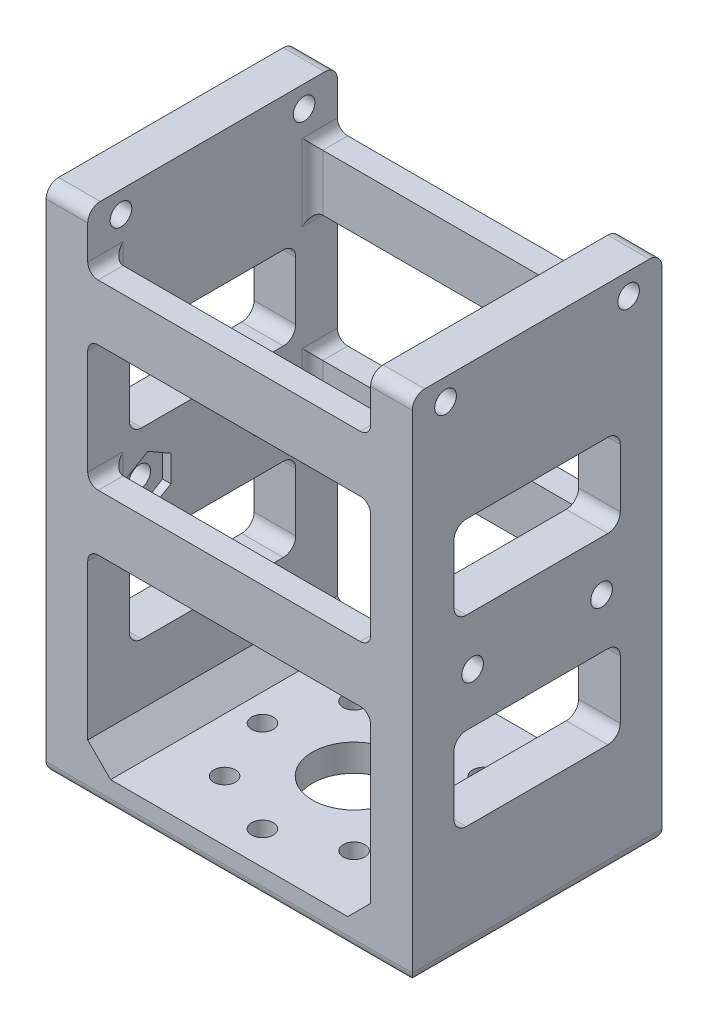
SolidWorks part; units mm, degrees
ref_plane "Front Plane" through (0, 0, 0) normal (0, 0, 1) x (1, 0, 0)
ref_plane "Top Plane" through (0, 0, 0) normal (0, 1, 0) x (1, 0, 0)
ref_plane "Right Plane" through (0, 0, 0) normal (1, 0, 0) x (0, 0, -1)
sketch "Sketch1" plane through (0, 0, 0) normal (0, 1, 0) x (1, 0, 0)
  line L1 (0, 0) -> (44, 0)
  line L2 (0, 0) -> (0, 30)
  line L3 (0, 30) -> (44, 30)
  line L4 (44, 0) -> (44, 30)
  dimension "D1" = 30
  dimension "D2" = 44
extrude "Boss-Extrude1" add sketch "Sketch1" along normal blind 54.5
sketch "Sketch5" plane through (0, 54.5, 0) normal (0, 1, 0) x (1, 0, 0)
  line L0 (0, 0) -> (44, 0) construction
  line L1 (0, 30) -> (5, 30)
  line L2 (0, 30) -> (0, 0)
  line L3 (0, 0) -> (5, 0)
  line L4 (5, 30) -> (5, 0)
  dimension "D1" = 5
ref_plane "Plane1" through (22, 0, 0) normal (-1, 0, 0) x (0, 0, 1)
extrude "Boss-Extrude3" add sketch "Sketch5" along normal blind 6.8
sketch "Sketch9" plane through (5, 0, 0) normal (1, 0, 0) x (0, 0, -1)
  line L0 (30, 61.3) -> (30, 54.5) construction
  line L2 (0, 61.3) -> (0, 54.5) construction
  line L4 (0, 61.3) -> (30, 61.3) construction
  circle A0 centre (26, 58.7) radius 1.3
  circle A1 centre (4, 58.7) radius 1.3
  dimension "D1" = 2.6
  dimension "D2" = 4
  dimension "D3" = 2.6
  dimension "D4" = 2.6
  dimension "D5" = 4
  dimension "D6" = 2.6
extrude "Cut-Extrude6" cut sketch "Sketch9" against normal through all
mirror "Mirror2" about plane through (22, 0, 0) normal (-1, 0, 0) of "Boss-Extrude3", "Cut-Extrude6"
fillet "Fillet1" radius 1.5 4 edges at (41.5, 61.3, -30) (2.5, 61.3, -30) (2.5, 61.3, 0) (41.5, 61.3, 0)
fillet "Fillet2" radius 1.25 4 edges at (0, 0, -15) (22, 0, -30) (22, 0, 0) (44, 0, -15)
sketch "Sketch11" plane through (0, 54.5, 0) normal (0, 1, 0) x (1, 0, 0)
  line L0 (39, 0) -> (39, 30) construction
  line L1 (39, 27) -> (5, 27)
  line L2 (39, 27) -> (39, 3)
  line L3 (39, 3) -> (5, 3)
  line L4 (5, 27) -> (5, 3)
  line L5 (5, 0) -> (5, 30) construction
  line L6 (39, 30) -> (5, 30) construction
  line L7 (5, 0) -> (39, 0) construction
  dimension "D1" = 3
  dimension "D2" = 3
extrude "Cut-Extrude7" cut sketch "Sketch11" against normal blind 51.25
ref_point "Point1"
sketch "Sketch13" plane through (0, 0, 0) normal (0, -1, 0) x (1, 0, 0)
  circle A0 centre (22, -15) radius 5
  circle A1 centre (33, -15) radius 1.3
  dimension "D1" = 10
  dimension "D2" = 2.6
  dimension "D3" = 11
extrude "Cut-Extrude8" cut sketch "Sketch13" against normal blind 3.5
ref_axis "Axis1" through (22, 0, -15) along (0, -1, 0)
pattern_circular "CirPattern1" count 8 over 360 about axis through (22, 0, -15) along (0, -1, 0) of "Cut-Extrude8"
ref_plane "Plane2" through (0, 0, -15) normal (0, 0, -1) x (-1, 0, 0)
sketch "Sketch15" plane through (44, 0, 0) normal (1, 0, 0) x (0, 0, -1)
  line L0 (0, 1.25) -> (30, 1.25) construction
  line L1 (25, 13.25) -> (5, 13.25)
  line L2 (25, 13.25) -> (25, 23.25)
  line L3 (25, 23.25) -> (5, 23.25)
  line L4 (5, 13.25) -> (5, 23.25)
  line L5 (30, 59.8) -> (30, 1.25) construction
  line L6 (0, 59.8) -> (0, 1.25) construction
  line L8 (25, 35.25) -> (5, 35.25)
  line L9 (25, 35.25) -> (25, 45.25)
  line L10 (25, 45.25) -> (5, 45.25)
  line L11 (5, 35.25) -> (5, 45.25)
  dimension "D1" = 12
  dimension "D2" = 10
  dimension "D3" = 5
  dimension "D4" = 5
  dimension "D5" = 12
  dimension "D6" = 10
extrude "Cut-Extrude10" cut sketch "Sketch15" against normal up to next
fillet "Fillet6" radius 1.5 8 edges at (41.5, 13.25, -5) (41.5, 35.25, -5) (41.5, 23.25, -5) (41.5, 45.25, -5) (41.5, 23.25, -25) (41.5, 45.25, -25) (41.5, 35.25, -25) (41.5, 13.25, -25)
mirror "Mirror4" about plane through (22, 0, 0) normal (-1, 0, 0) of "Cut-Extrude10", "Fillet6"
sketch "Sketch16" plane through (0, 0, 0) normal (0, 0, 1) x (1, 0, 0)
  line L5 (5, 54.5) -> (39, 54.5) construction
  line L7 (5, 47.75) -> (39, 47.75)
  line L8 (5, 47.75) -> (5, 32.625)
  line L9 (5, 32.625) -> (39, 32.625)
  line L10 (39, 47.75) -> (39, 32.625)
  line L15 (5, 25.875) -> (39, 25.875)
  line L16 (5, 25.875) -> (5, 3.25)
  line L17 (5, 3.25) -> (39, 3.25)
  line L18 (39, 25.875) -> (39, 3.25)
  line L19 (42.75, 0) -> (1.25, 0) construction
  line L20 (39, 59.8) -> (39, 54.5) construction
  line L21 (5, 59.8) -> (5, 54.5) construction
  dimension "D1" = 6.75
  dimension "D2" = 3.25
  dimension "D3" = 6.75
  dimension "D4" = 15.125
extrude "Cut-Extrude11" cut sketch "Sketch16" against normal up to next
mirror "Mirror5" about plane through (0, 0, -15) normal (0, 0, -1) of "Cut-Extrude11"
fillet "Fillet7" radius 1.25 24 edges at (5, 47.75, -28.5) (5, 47.75, -1.5) (5, 54.5, -1.5) (5, 54.5, -28.5) (39, 54.5, -1.5) (39, 54.5, -28.5) (39, 47.75, -28.5) (39, 47.75, -1.5) (5, 29.25, -3) (39, 29.25, -3) (39, 51.125, -3) (5, 51.125, -3) (5, 51.125, -27) (39, 51.125, -27) (39, 29.25, -27) (5, 29.25, -27) (39, 25.875, -1.5) (39, 25.875, -28.5) (5, 25.875, -28.5) (5, 25.875, -1.5) (5, 32.625, -28.5) (39, 32.625, -28.5) (39, 32.625, -1.5) (5, 32.625, -1.5)
chamfer "Chamfer1" distance 2.75 angle 45 2 edges at (5, 3.25, -15) (39, 3.25, -15)
sketch "Sketch18" plane through (0, 0, 0) normal (-1, 0, 0) x (0, 0, 1)
  line L0 (-30, 59.8) -> (-30, 1.25) construction
  line L3 (-6.5, 35.25) -> (-23.5, 35.25) construction
  circle A0 centre (-22.75, 29.25) radius 1.3
  circle A1 centre (-7.25, 29.25) radius 1.3
  dimension "D1" = 2.6
  dimension "D2" = 2.6
  dimension "D3" = 15.5
  dimension "D4" = 7.25
  dimension "D5" = 6
  dimension "D6" = 6
extrude "Cut-Extrude12" cut sketch "Sketch18" against normal blind 5
sketch "Sketch19" plane through (5, 0, 0) normal (1, 0, 0) x (0, 0, -1)
  line L0 (4.25, 33.875) -> (4.25, 24.625) construction
  line L1 (7.25, 26.0746) -> (10, 27.6623)
  line L2 (10, 27.6623) -> (10, 30.8377)
  line L3 (10, 30.8377) -> (7.25, 32.4254)
  line L4 (7.25, 32.4254) -> (4.5, 30.8377)
  line L5 (4.5, 30.8377) -> (4.5, 27.6623)
  line L6 (4.5, 27.6623) -> (7.25, 26.0746)
  line L7 (22.75, 26.0746) -> (25.5, 27.6623)
  line L8 (25.5, 27.6623) -> (25.5, 30.8377)
  line L9 (25.5, 30.8377) -> (22.75, 32.4254)
  line L10 (22.75, 32.4254) -> (20, 30.8377)
  line L11 (20, 30.8377) -> (20, 27.6623)
  line L12 (20, 27.6623) -> (22.75, 26.0746)
  circle A0 centre (7.25, 29.25) radius 2.75 construction
  circle A1 centre (22.75, 29.25) radius 2.75 construction
extrude "Cut-Extrude13" cut sketch "Sketch19" against normal blind 1
mirror "Mirror6" about plane through (22, 0, 0) normal (-1, 0, 0) of "Cut-Extrude13", "Cut-Extrude12"
equation "\"D4@Sketch18\"=(30-\"D3@Sketch18\")/2"
